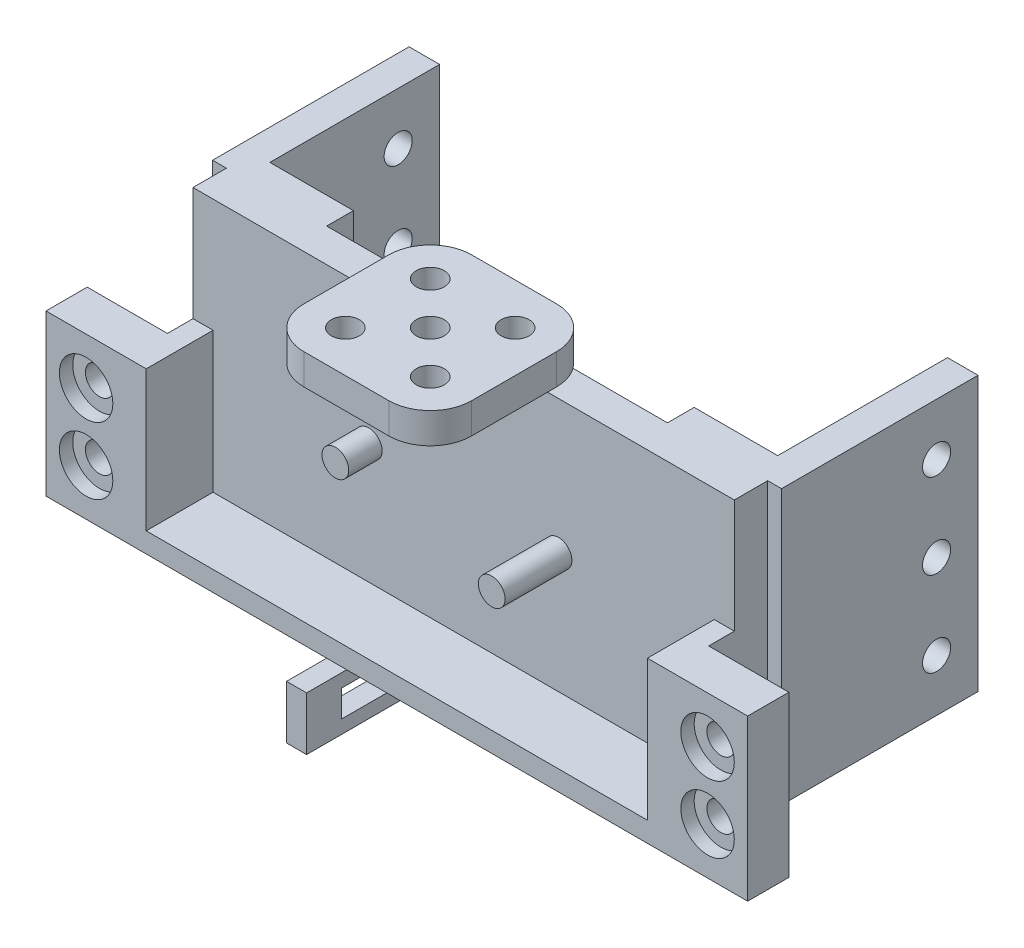
SolidWorks part; units mm, degrees
ref_plane "Front Plane" through (0, 0, 0) normal (0, 0, 1) x (1, 0, 0)
ref_plane "Top Plane" through (0, 0, 0) normal (0, 1, 0) x (1, 0, 0)
ref_plane "Right Plane" through (0, 0, 0) normal (1, 0, 0) x (0, 0, -1)
sketch "Sketch1" plane through (0, 0, 0) normal (0, 0, 1) x (1, 0, 0)
  line L1 (-37.5, -17.5) -> (37.5, -17.5)
  line L2 (-37.5, -17.5) -> (-37.5, 17.5)
  line L3 (-37.5, 17.5) -> (37.5, 17.5)
  line L4 (37.5, -17.5) -> (37.5, 17.5)
  line L5 (-37.5, -17.5) -> (37.5, 17.5) construction
  line L6 (-37.5, 17.5) -> (37.5, -17.5) construction
  point P0 (0, 0)
  dimension "D1" = 75
  dimension "D2" = 35
extrude "Boss-Extrude1" add sketch "Sketch1" along normal blind 5
sketch "Sketch2" plane through (0, 0, 5) normal (0, 0, 1) x (1, 0, 0)
  circle A0 centre (-14.2, 0.5) radius 2
  circle A1 centre (14.2, 0.5) radius 2
  dimension "D4" = 4
  dimension "D5" = 4
extrude "Boss-Extrude2" add sketch "Sketch2" along normal blind 10
sketch "Sketch3" plane through (0, 0, 0) normal (0, 0, -1) x (-1, 0, 0)
  line L1 (-37.5, 17.5) -> (37.5, 17.5)
  line L2 (-37.5, 17.5) -> (-37.5, -17.5)
  line L3 (-37.5, -17.5) -> (37.5, -17.5)
  line L4 (37.5, 17.5) -> (37.5, -17.5)
  line L5 (-37.5, 20.5) -> (-40.5, 20.5)
  line L6 (40.5, -17.5) -> (40.5, -20.5)
  line L8 (-40.5, 20.5) -> (40.5, 20.5)
  line L9 (-40.5, 20.5) -> (-40.5, -20.5)
  line L10 (-40.5, -20.5) -> (40.5, -20.5)
  line L11 (40.5, 20.5) -> (40.5, -20.5)
  line M1 (-37.5, 17.5) -> (-37.5, -17.5)
  line M2 (-37.5, -17.5) -> (37.5, -17.5)
  line M3 (37.5, -17.5) -> (37.5, 17.5)
  line M4 (37.5, 17.5) -> (-37.5, 17.5)
extrude "Boss-Extrude3" add sketch "Sketch3" against normal blind 15 contours L11 L8 L5 L9 L10 L6 M1 M4 M3 M2 region at (-1.5, 19.5921, 0)
sketch "Sketch4" plane through (0, 20.5, 0) normal (0, 1, 0) x (1, 0, 0)
  line L0 (-37.5, -5) -> (-37.5, -12.5)
  line L2 (-37.5, -15) -> (37.5, -15)
  line L4 (37.5, -5) -> (37.5, -12.5)
  line L5 (-37.5, -14) -> (-37.5, -15)
  line L12 (-37.5, -12.5) -> (-37.5, -14)
  line L14 (37.5, -14) -> (37.5, -12.5)
  line L16 (37.5, -15) -> (37.5, -14)
  line L17 (-37.5, -5) -> (37.5, -5)
  dimension "D2" = 1
  dimension "D3" = 1.5
extrude "Cut-Extrude2" cut sketch "Sketch4" against normal blind 10
sketch "Sketch8" plane through (0, 20.5, 0) normal (0, 1, 0) x (1, 0, 0)
  line L0 (0, -5) -> (0, 2.55)
  line L1 (37.5, -5) -> (-37.5, -5) construction
  line L3 (0, -5) -> (0, -15)
  line L4 (0, -15) -> (0, -22.55)
  line L16 (0, 2.55) -> (-12.55, 2.55)
  line L17 (0, 2.55) -> (12.55, 2.55)
  line L18 (0, -22.55) -> (-12.55, -22.55)
  line L19 (0, -22.55) -> (12.55, -22.55)
  line L21 (-12.55, 2.55) -> (12.55, 2.55)
  line L22 (-12.55, 2.55) -> (-12.55, -22.55)
  line L23 (-12.55, -22.55) -> (12.55, -22.55)
  line L24 (12.55, 2.55) -> (12.55, -22.55)
  line M6 (-37.5, -5) -> (37.5, -5)
  line M10 (40.5, 0) -> (-40.5, 0)
  dimension "D1" = 7.55
  dimension "D2" = 10
  dimension "D3" = 7.55
  dimension "D5" = 12.55
extrude "Boss-Extrude6" add sketch "Sketch8" along normal blind 4.57 contours L22 L18 L4 L3 M6 | L24 L3 L4 L19 M6 | L22 L0 M10 M6 | L16 L22 L0 M10 | L24 L17 L0 M10 | L24 L0 M10 M6 region at (-6.275, 20.5, 2.5) region at (6.275, 20.5, 13.775) region at (-6.275, 20.5, 13.775) region at (6.275, 20.5, 2.5) region at (-6.275, 20.5, -1.275) region at (6.275, 20.5, -1.275)
sketch "Sketch9" plane through (0, 25.07, 0) normal (0, 1, 0) x (1, 0, 0)
  circle A0 centre (0, -10) radius 2.1
  circle A1 centre (-6.3498, -3.6502) radius 2.1
  circle A2 centre (6.3498, -3.6502) radius 2.1
  circle A3 centre (6.3498, -16.3498) radius 2.1
  circle A4 centre (-6.3498, -16.3498) radius 2.1
  dimension "D1" = 4.2
  dimension "D2" = 4.2
  dimension "D3" = 4.2
  dimension "D4" = 4.2
  dimension "D5" = 4.2
  dimension "D6" = 8.98
  dimension "D7" = 8.98
  dimension "D8" = 8.98
  dimension "D9" = 8.98
extrude "Cut-Extrude3" cut sketch "Sketch9" against normal blind 4.57
sketch "Sketch14" plane through (0, 20.5, 0) normal (0, 1, 0) x (1, 0, 0)
  line L1 (-37.5, -5) -> (-40.5, -5)
  line L2 (-37.5, -5) -> (-37.5, -15)
  line L3 (-37.5, -15) -> (-40.5, -15)
  line L4 (-40.5, -5) -> (-40.5, -15)
  line L5 (37.5, -5) -> (40.5, -5)
  line L6 (37.5, -5) -> (37.5, -15)
  line L7 (37.5, -15) -> (40.5, -15)
  line L8 (40.5, -5) -> (40.5, -15)
extrude "Cut-Extrude5" cut sketch "Sketch14" against normal blind 17
sketch "Sketch15" plane through (0, 20.5, 0) normal (0, 1, 0) x (1, 0, 0)
  circle A0 centre (-6.3498, -3.6502) radius 2.75
  circle A1 centre (6.3498, -3.6502) radius 2.75
  dimension "D1" = 5.5
  dimension "D2" = 5.5
extrude "Cut-Extrude6" cut sketch "Sketch15" against normal blind 1.5
fillet "Fillet1" radius 1 4 edges at (-8.7458, 19.75, 5) (3.9539, 19.75, 5) (8.7458, 19.75, 5) (-3.9539, 19.75, 5)
sketch "Sketch19" plane through (0, 0, 15) normal (0, 0, 1) x (1, 0, 0)
  circle A0 centre (-14.2, 0.5) radius 2
extrude "Cut-Extrude7" cut sketch "Sketch19" against normal blind 5
sketch "Sketch20" plane through (40.5, 0, 0) normal (1, 0, 0) x (0, 0, -1)
  line L0 (-15, 3.5) -> (-5, 3.5) construction
  line L1 (-15, -20.5) -> (-8.83, -20.5)
  line L2 (-15, -20.5) -> (-15, 3.5)
  line L3 (-15, 3.5) -> (-8.83, 3.5)
  line L4 (-8.83, -20.5) -> (-8.83, 3.5)
  dimension "D1" = 6.17
extrude "Boss-Extrude7" add sketch "Sketch20" along normal blind 12
sketch "Sketch21" plane through (-40.5, 0, 0) normal (-1, 0, 0) x (0, 0, 1)
  line L0 (15, -20.5) -> (0, -20.5) construction
  line L1 (15, 3.5) -> (8.83, 3.5)
  line L2 (15, 3.5) -> (15, -20.5)
  line L3 (15, -20.5) -> (8.83, -20.5)
  line L4 (8.83, 3.5) -> (8.83, -20.5)
  dimension "D1" = 6.17
extrude "Boss-Extrude8" add sketch "Sketch21" along normal blind 12
sketch "Sketch24" plane through (0, 0, 8.83) normal (0, 0, -1) x (-1, 0, 0)
  line L0 (-46.5, 3.5) -> (-46.5, -5.6) construction
  line L1 (-46.5, -5.6) -> (-46.5, 3.5) construction
  line L2 (-46.5, -10.6) -> (-46.5, -20.5) construction
  line L3 (-52.5, 3.5) -> (-40.5, 3.5) construction
  line L4 (-46.5, -10.6) -> (-46.5, -20.5) construction
  line L5 (46.5, -10.6) -> (46.5, -20.5) construction
  line L6 (-52.5, -20.5) -> (-40.5, -20.5) construction
  line L7 (46.5, 3.5) -> (46.5, -6.4) construction
  line L8 (52.5, 3.5) -> (40.5, 3.5) construction
  line L9 (52.5, -20.5) -> (40.5, -20.5) construction
  circle A1 centre (-46.5, -3.5) radius 2.1
  circle A2 centre (-46.5, -13.5) radius 2.1
  circle A4 centre (46.5, -3.5) radius 2.1
  circle A5 centre (46.5, -13.5) radius 2.1
  point P18 (0, 0)
  point P19 (0, 0)
  dimension "D1" = 4.2
  dimension "D2" = 7
  dimension "D3" = 4.2
  dimension "D4" = 4.2
  dimension "D5" = 9.9
  dimension "D6" = 4.2
  dimension "D7" = 7
  dimension "D8" = 7
  dimension "D9" = 7
extrude "Cut-Extrude8" cut sketch "Sketch24" against normal through all
sketch "Sketch25" plane through (0, 0, 15) normal (0, 0, 1) x (1, 0, 0)
  circle A6 centre (-46.5, -3.5) radius 4
  circle A7 centre (-46.5, -13.5) radius 4
  circle A8 centre (46.5, -13.5) radius 4
  circle A9 centre (46.5, -3.5) radius 4
  dimension "D1" = 8
  dimension "D2" = 8
  dimension "D3" = 8
  dimension "D4" = 8
extrude "Cut-Extrude9" cut sketch "Sketch25" against normal blind 2
sketch "Sketch26" plane through (0, -20.5, 0) normal (0, -1, 0) x (1, 0, 0)
  line L0 (0, 15) -> (-7.5, 15)
  line L1 (52.5, 15) -> (-52.5, 15) construction
  line L2 (-7.5, 15) -> (-7.5, 0)
  line L3 (40.5, 0) -> (-40.5, 0) construction
  line L5 (-7.5, 0) -> (-10.5, 0)
  line L6 (-7.5, 0) -> (-7.5, 21)
  line L7 (-7.5, 21) -> (-10.5, 21)
  line L8 (-10.5, 0) -> (-10.5, 21)
  line M4 (-40.5, 0) -> (40.5, 0)
  line M8 (52.5, 15) -> (-52.5, 15)
  dimension "D1" = 3
  dimension "D2" = 21
  dimension "D3" = 7.5
extrude "Boss-Extrude9" add sketch "Sketch26" along normal blind 8 contours L8 L2 M4 M8 | L8 L6 L7 M8 region at (-9, -20.5, 18) region at (-9, -20.5, 7.5)
sketch "Sketch27" plane through (-10.5, 0, 0) normal (-1, 0, 0) x (0, 0, 1)
  line L0 (21, -28.5) -> (0, -20.5) construction
  line L1 (0, -28.5) -> (21, -20.5) construction
  line L3 (5.25, -26.5) -> (15.75, -26.5)
  line L4 (5.25, -26.5) -> (5.25, -22.5)
  line L5 (5.25, -22.5) -> (15.75, -22.5)
  line L6 (15.75, -26.5) -> (15.75, -22.5)
  line L7 (5.25, -26.5) -> (15.75, -22.5) construction
  line L8 (5.25, -22.5) -> (15.75, -26.5) construction
  point P8 (10.5, -24.5)
  dimension "D1" = 4
extrude "Cut-Extrude10" cut sketch "Sketch27" against normal through all
sketch "Sketch28" plane through (0, -20.5, 0) normal (0, -1, 0) x (1, 0, 0)
  line L0 (-25.5, 0) -> (-42.57, 0)
  line L1 (-10.5, 0) -> (-40.5, 0) construction
  line L2 (-42.57, 0) -> (-42.57, -29.4)
  line L3 (25.5, 0) -> (42.57, 0)
  line L4 (40.5, 0) -> (-7.5, 0) construction
  line L5 (42.57, 0) -> (42.57, -29.4)
  line L6 (-42.57, -29.4) -> (-38, -29.4)
  line L7 (-38, -29.4) -> (-38, -4)
  line L8 (-38, -4) -> (-25.5, -4)
  line L9 (-25.5, -4) -> (-25.5, 0)
  line L10 (42.57, -29.4) -> (38, -29.4)
  line L11 (38, -29.4) -> (38, -4)
  line L12 (38, -4) -> (25.5, -4)
  line L13 (25.5, -4) -> (25.5, 0)
  line L14 (40.5, 8.83) -> (40.5, 0) construction
  line L15 (-40.5, 8.83) -> (-40.5, 0) construction
  dimension "D1" = 29.4
  dimension "D2" = 29.4
  dimension "D3" = 81
  dimension "D4" = 4
  dimension "D5" = 4
  dimension "D6" = 4.57
  dimension "D7" = 4.57
  dimension "D8" = 15
  dimension "D9" = 15
  dimension "D10" = 38
  dimension "D11" = 38
extrude "Boss-Extrude10" add sketch "Sketch28" against normal blind 41
sketch "Sketch30" plane through (-38, 0, 0) normal (1, 0, 0) x (0, 0, -1)
  line L1 (29.4, 0) -> (23.2, 0)
  line L2 (29.4, 20.5) -> (29.4, -20.5) construction
  circle A0 centre (23.2, 0) radius 2.1
  circle A1 centre (23.2, 12.7) radius 2.1
  circle A2 centre (23.2, -12.7) radius 2.1
  dimension "D2" = 4.2
  dimension "D3" = 4.2
  dimension "D4" = 4.2
  dimension "D1" = 6.2
  dimension "D5" = 12.7
  dimension "D6" = 12.7
extrude "Cut-Extrude11" cut sketch "Sketch30" along normal through all and the other way through all contours A2 | A0 | A1 region at (-38, 0, -21.1594) region at (-38, 12.7, -23.2) region at (-38, -12.7, -23.2)
fillet "Fillet2" radius 6.2 4 edges at (-12.55, 22.785, -2.55) (12.55, 22.785, -2.55) (12.55, 22.785, 22.55) (-12.55, 22.785, 22.55)
